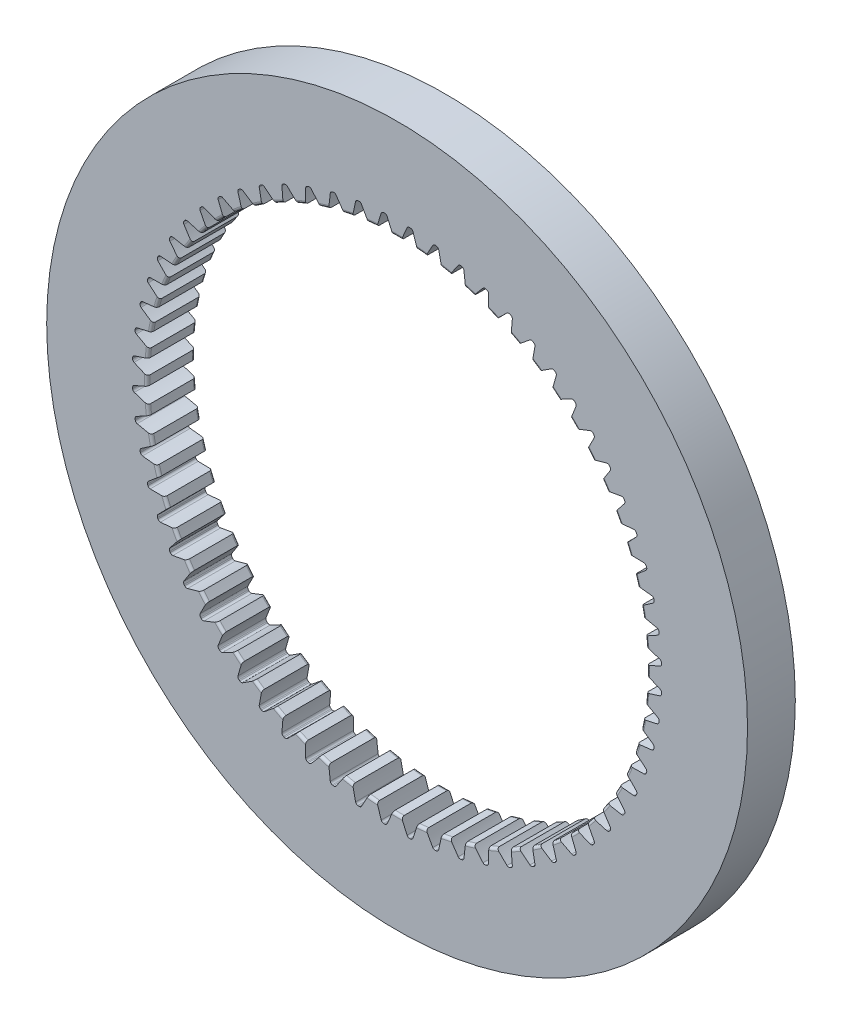
SolidWorks part; units mm, degrees
ref_plane "Front Plane" through (0, 0, 0) normal (0, 0, 1) x (1, 0, 0)
ref_plane "Top Plane" through (0, 0, 0) normal (0, 1, 0) x (1, 0, 0)
ref_plane "Right Plane" through (0, 0, 0) normal (1, 0, 0) x (0, 0, -1)
sketch "Sketch1" plane through (0, 0, 0) normal (0, 0, 1) x (1, 0, 0)
  line L0 (0, 0) -> (0, 25.4) construction
  line L1 (-8.1634, 28.3712) -> (8.1634, 22.4288) construction
  circle A0 centre (0, 0) radius 26.1937 construction
  circle A1 centre (0, 0) radius 26.3922 construction
  circle A2 centre (0, 0) radius 25.4 construction
  circle A3 centre (0, 0) radius 23.8682 construction
  circle A4 centre (0, 0) radius 34.925 construction
  circle A5 centre (0, 0) radius 24.9047 construction
  point P8 (406.4, 0)
  point P13 (812.8, 0)
  dimension "Outside Diameter" = 52.7844
  dimension "Root Diameter" = 52.3875
  dimension "Gear Pitch Diameter" = 50.8
  dimension "ID | Base Diameter" = 47.7364
  dimension "OD" = 69.85
  dimension "ID" = 49.8094
  dimension "Pressure Angle" = 20
  dimension "Number of Teeth" = 1625.6
  dimension "Gear Pitch | Diametral Pitch" = 812.8
sketch "Sketch2" plane through (0, 0, 0) normal (1, 0, 0) x (0, 0, -1)
  line L0 (-2.3813, 0) -> (2.3813, 0) construction
  dimension "Face Width" = 4.7625
sketch "Sketch3" plane through (0, 0, 0) normal (0, 0, 1) x (1, 0, 0)
  circle A0 centre (0, 0) radius 34.925
  circle A1 centre (0, 0) radius 24.9047 construction
  circle A2 centre (0, 0) radius 24.9047
  circle A4 centre (0, 0) radius 34.925 construction
extrude "Boss-Extrude1" add sketch "Sketch3" against normal up to vertex (2.3813 mm away) and the other way up to vertex (2.3813 mm away) up to point (0, 0, -2.3813) other way up to point (0, 0, 2.3813)
fillet "Fillet1" radius 0.2663 2 edges at (24.9047, 0, -2.3813) (24.9047, 0, 2.3813)
sketch "Sketch4" plane through (0, 0, 0) normal (0, 0, 1) x (1, 0, 0)
  line L2 (0, 0) -> (23.8671, -0.2301) construction
  line L3 (0, 0) -> (23.8671, 0.2301) construction
  line L4 (0, 0) -> (23.7747, -2.1104) construction
  circle A4 centre (0, 0) radius 23.8682 construction
  circle A5 centre (0, 0) radius 26.3922 construction
  arc A7 (26.3704, -1.0718) -> (26.3485, -1.5181) centre (0, 0) cw
  arc A8 (23.8671, -0.2301) -> (23.7747, -2.1104) centre (0, 0) cw
  spline S0 degree 4 poles (23.8671, 0.2301) (23.871, 0.2301) (23.882, 0.2305) (23.9029, 0.2316) (23.9368, 0.2341) (23.9801, 0.2383) (24.036, 0.2449) (24.1018, 0.2541) (24.1741, 0.2658) (24.2528, 0.2802) (24.3312, 0.2961) (24.4093, 0.3132) (24.4871, 0.3316) (24.5813, 0.3554) (24.6942, 0.3859) (24.826, 0.4245) (24.9753, 0.4719) (25.1273, 0.5239) (25.2767, 0.5782) (25.4275, 0.6367) (25.5732, 0.6958) (25.7243, 0.7608) (25.8637, 0.8227) (26.0197, 0.8961) (26.1454, 0.9566) (26.311, 1.0406) (26.4087, 1.0916) (26.523, 1.1527) (26.5736, 1.1806) (26.6049, 1.1978) knots 0 0 0 0 0 0.005377 0.015084 0.028532 0.04661 0.064855 0.092111 0.119476 0.146842 0.174209 0.201575 0.228941 0.256307 0.307035 0.361767 0.4165 0.471232 0.525964 0.580697 0.635429 0.690161 0.744894 0.799626 0.854358 0.909091 0.954545 1 1 1 1 1 construction
  spline S1 degree 4 poles (23.8671, 0.2301) (23.871, 0.2301) (23.882, 0.2305) (23.9029, 0.2316) (23.9368, 0.2341) (23.9801, 0.2383) (24.036, 0.2449) (24.1018, 0.2541) (24.1741, 0.2658) (24.2528, 0.2802) (24.3312, 0.2961) (24.4093, 0.3132) (24.4871, 0.3316) (24.5813, 0.3554) (24.6942, 0.3859) (24.826, 0.4245) (24.9753, 0.4719) (25.1273, 0.5239) (25.2767, 0.5782) (25.4275, 0.6367) (25.5732, 0.6958) (25.7243, 0.7608) (25.8637, 0.8227) (26.0197, 0.8961) (26.1454, 0.9566) (26.2751, 1.0224) (26.3382, 1.0549) (26.3704, 1.0718) knots 0 0 0 0 0 0.005377 0.015084 0.028532 0.04661 0.064855 0.092111 0.119476 0.146842 0.174209 0.201575 0.228941 0.256307 0.307035 0.361767 0.4165 0.471232 0.525964 0.580697 0.635429 0.690161 0.744894 0.799626 0.854358 0.909091 0.909091 0.909091 0.909091 0.909091 construction
  spline S2 degree 4 poles (23.8671, -0.2301) (23.871, -0.2301) (23.882, -0.2305) (23.9029, -0.2316) (23.9368, -0.2341) (23.9801, -0.2383) (24.036, -0.2449) (24.1018, -0.2541) (24.1741, -0.2658) (24.2528, -0.2802) (24.3312, -0.2961) (24.4093, -0.3132) (24.4871, -0.3316) (24.5813, -0.3554) (24.6942, -0.3859) (24.826, -0.4245) (24.9753, -0.4719) (25.1273, -0.5239) (25.2767, -0.5782) (25.4275, -0.6367) (25.5732, -0.6958) (25.7243, -0.7608) (25.8637, -0.8227) (26.0197, -0.8961) (26.1454, -0.9566) (26.311, -1.0406) (26.4087, -1.0916) (26.523, -1.1527) (26.5736, -1.1806) (26.6049, -1.1978) knots 0 0 0 0 0 0.005377 0.015084 0.028532 0.04661 0.064855 0.092111 0.119476 0.146842 0.174209 0.201575 0.228941 0.256307 0.307035 0.361767 0.4165 0.471232 0.525964 0.580697 0.635429 0.690161 0.744894 0.799626 0.854358 0.909091 0.954545 1 1 1 1 1 construction
  spline S3 degree 4 poles (23.8671, -0.2301) (23.871, -0.2301) (23.882, -0.2305) (23.9029, -0.2316) (23.9368, -0.2341) (23.9801, -0.2383) (24.036, -0.2449) (24.1018, -0.2541) (24.1741, -0.2658) (24.2528, -0.2802) (24.3312, -0.2961) (24.4093, -0.3132) (24.4871, -0.3316) (24.5813, -0.3554) (24.6942, -0.3859) (24.826, -0.4245) (24.9753, -0.4719) (25.1273, -0.5239) (25.2767, -0.5782) (25.4275, -0.6367) (25.5732, -0.6958) (25.7243, -0.7608) (25.8637, -0.8227) (26.0197, -0.8961) (26.1454, -0.9566) (26.2751, -1.0224) (26.3382, -1.0549) (26.3704, -1.0718) knots 0 0 0 0 0 0.005377 0.015084 0.028532 0.04661 0.064855 0.092111 0.119476 0.146842 0.174209 0.201575 0.228941 0.256307 0.307035 0.361767 0.4165 0.471232 0.525964 0.580697 0.635429 0.690161 0.744894 0.799626 0.854358 0.909091 0.909091 0.909091 0.909091 0.909091
  spline S4 degree 4 poles (23.7747, -2.1104) (23.7786, -2.1107) (23.7896, -2.1115) (23.8105, -2.1124) (23.8445, -2.1132) (23.888, -2.1133) (23.9443, -2.1122) (24.0107, -2.1095) (24.0838, -2.105) (24.1634, -2.0983) (24.243, -2.0902) (24.3225, -2.0808) (24.4017, -2.0701) (24.4978, -2.0558) (24.6131, -2.0365) (24.7481, -2.0109) (24.9013, -1.9784) (25.0577, -1.9415) (25.2117, -1.9021) (25.3675, -1.8587) (25.5183, -1.8142) (25.675, -1.7643) (25.8198, -1.7163) (25.9822, -1.6586) (26.1133, -1.6107) (26.2863, -1.5433) (26.3885, -1.5022) (26.5082, -1.4526) (26.5614, -1.4298) (26.5942, -1.4157) knots 0 0 0 0 0 0.005377 0.015084 0.028532 0.04661 0.064855 0.092111 0.119476 0.146842 0.174209 0.201575 0.228941 0.256307 0.307035 0.361767 0.4165 0.471232 0.525964 0.580697 0.635429 0.690161 0.744894 0.799626 0.854358 0.909091 0.954545 1 1 1 1 1 construction
  spline S5 degree 4 poles (23.7747, -2.1104) (23.7786, -2.1107) (23.7896, -2.1115) (23.8105, -2.1124) (23.8445, -2.1132) (23.888, -2.1133) (23.9443, -2.1122) (24.0107, -2.1095) (24.0838, -2.105) (24.1634, -2.0983) (24.243, -2.0902) (24.3225, -2.0808) (24.4017, -2.0701) (24.4978, -2.0558) (24.6131, -2.0365) (24.7481, -2.0109) (24.9013, -1.9784) (25.0577, -1.9415) (25.2117, -1.9021) (25.3675, -1.8587) (25.5183, -1.8142) (25.675, -1.7643) (25.8198, -1.7163) (25.9822, -1.6586) (26.1133, -1.6107) (26.2488, -1.5579) (26.3148, -1.5317) (26.3485, -1.5181) knots 0 0 0 0 0 0.005377 0.015084 0.028532 0.04661 0.064855 0.092111 0.119476 0.146842 0.174209 0.201575 0.228941 0.256307 0.307035 0.361767 0.4165 0.471232 0.525964 0.580697 0.635429 0.690161 0.744894 0.799626 0.854358 0.909091 0.909091 0.909091 0.909091 0.909091
  point P11 (0, 0)
  dimension "D1" = 5.625
extrude "Cut-Extrude1" cut sketch "Sketch4" against normal through all both and the other way through all
fillet "Fillet2" radius 0.2663 2 edges at (26.3485, -1.5181, 0) (26.3704, -1.0718, 0)
pattern_circular "CirPattern1" count 64 over 360 about axis through (0, 0, 2.3813) along (0, 0, -1) of "Cut-Extrude1", "Fillet2"
equation "\"Root Diameter@Sketch1\"=\"Root Diameter\""
equation "\"Outside Diameter@Sketch1\" = \"Outside Diameter\""
equation "\"D1@CirPattern1\"=\"Number of Teeth\""
equation "\"Diametral Pitch\"= 32"
equation "\"Number of Teeth\"= 64"
equation "\"Pressure Angle\"=20"
equation "\"Pitch Diameter\"= \"Number of Teeth\" / \"Diametral Pitch\""
equation "\"Base Diameter\"= \"Pitch Diameter\" * cos ( \"Pressure Angle\" )"
equation "\"Outside Diameter\"= \"Pitch Diameter\" + ( 2 * \"Dedendum\" )"
equation "\"Dedendum\"= 1.25 / \"Diametral Pitch\""
equation "\"Root Diameter\"= \"Pitch Diameter\" + ( 2 * \"Addendum\" )"
equation "\"Pitch Angle\"= 360deg / \"Number of Teeth\""
equation "\"Alpha\"= sqr ( \"Pitch Diameter\" ^ 2 - \"Base Diameter\" ^ 2 ) / \"Base Diameter\" * 180 / PI - \"Pressure Angle\""
equation "\"Beta\"= ( \"Pitch Angle\" / 4 - \"Alpha\" )"
equation "\"Phi\"= sqr ( ( \"Outside Diameter\" / 2 ) ^ 2 - ( \"Base Diameter\" / 2 ) ^ 2 ) / ( \"Base Diameter\" / 2 )"
equation "\"Addendum\"= 1 / \"Diametral Pitch\""
equation "\"WorkingDepth\"= 2 / \"Diametral Pitch\""
equation "\"WholeDepth\"= 2.25 / \"Diametral Pitch\""
equation "\"Clearance\"= 0.25 / \"Diametral Pitch\""
equation "\"ToothThickness\"= ( pi * 2 ) / \"Diametral Pitch\""
equation "\"CircularPitch\"= pi / \"Diametral Pitch\""
equation "\"Number of Teeth@Sketch1\"=\"Number of Teeth\""
equation "\"Gear Pitch | Diametral Pitch@Sketch1\"=\"Diametral Pitch\""
equation "\"Pressure Angle@Sketch1\"=\"Pressure Angle\""
equation "\"Gear Pitch Diameter@Sketch1\"=\"Pitch Diameter\""
equation "\"ID | Base Diameter@Sketch1\" = \"Base Diameter\""
equation "\"Fillet\"= \"Clearance\" * cos ( \"Pressure Angle\" ) * tan ( ( 90 + \"Pressure Angle\" ) / 2 )"
equation "\"D1@Sketch4\"=360/\"Number of Teeth\""
equation "\"D1@Fillet1\" = \"Fillet\""
equation "\"D1@Fillet2\"=\"Fillet\""
